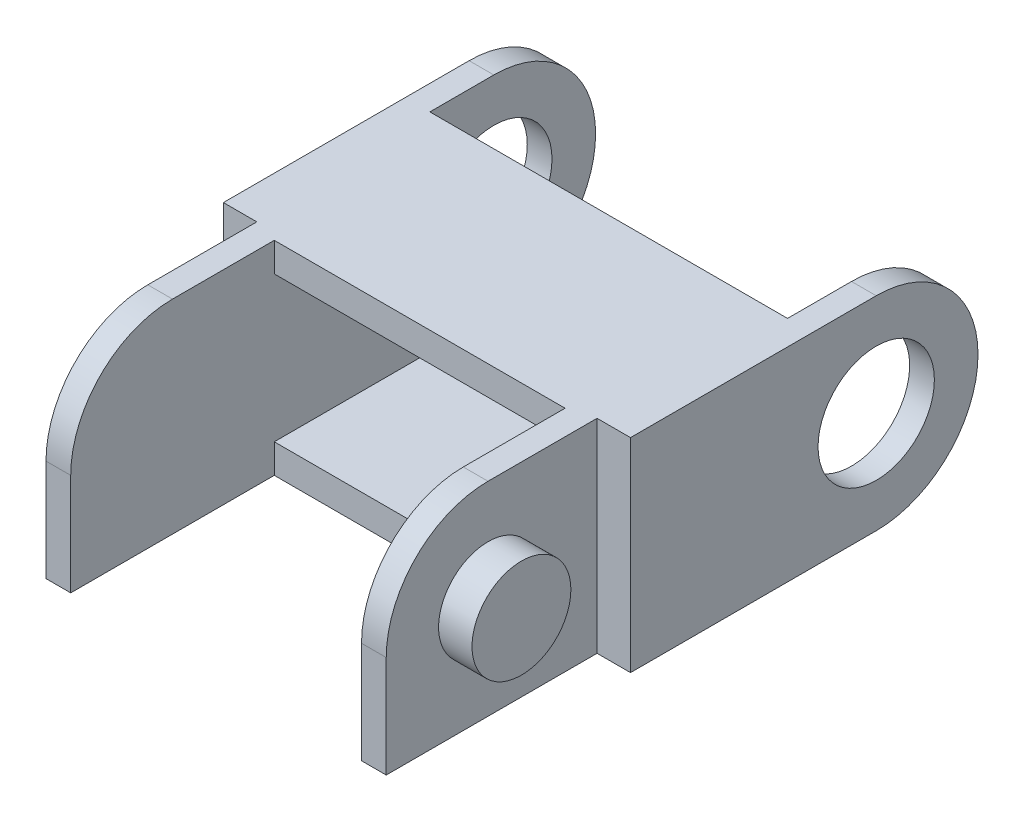
SolidWorks part; units mm, degrees
ref_plane "Front Plane" through (0, 0, 0) normal (0, 0, 1) x (1, 0, 0)
ref_plane "Top Plane" through (0, 0, 0) normal (0, 1, 0) x (1, 0, 0)
ref_plane "Right Plane" through (0, 0, 0) normal (1, 0, 0) x (0, 0, -1)
sketch "Sketch1" plane through (0, 0, 0) normal (0, 0, 1) x (1, 0, 0)
  line L0 (-12, 7) -> (12, 7)
  line L1 (-10, -5) -> (10, -5)
  line L2 (-10, -5) -> (-10, 5)
  line L3 (-10, 5) -> (10, 5)
  line L4 (10, -5) -> (10, 5)
  line L5 (-10, -5) -> (10, 5) construction
  line L6 (-10, 5) -> (10, -5) construction
  line L7 (12, -7) -> (12, 7)
  line L8 (-12, -7) -> (12, -7)
  line L9 (-12, -7) -> (-12, 7)
  point P0 (0, 0)
  dimension "D2" = 10
  dimension "D3" = 20
  dimension "D1" = 2
extrude "Boss-Extrude1" add sketch "Sketch1" along normal mid plane 10
sketch "Sketch3" plane through (12, 0, 0) normal (1, 0, 0) x (0, 0, -1)
  line L0 (-5, -7) -> (-5, 7)
  line L3 (-12, 7) -> (-5, 7)
  line L6 (-5, -7) -> (-19, -7)
  line L7 (-19, -7) -> (-19, 0)
  arc A1 (-19, 0) -> (-12, 7) centre (-12, 0) cw
extrude "Boss-Extrude3" add sketch "Sketch3" against normal blind 2
sketch "Sketch2" plane through (12, 0, 0) normal (1, 0, 0) x (0, 0, -1)
  line L4 (12.4, 7) -> (-5, 7)
  line L5 (-5, 7) -> (-5, -7)
  line L6 (-5, -7) -> (12.4, -7)
  line L9 (5.4, -7) -> (5.4, 7)
  line L10 (5.4, -7) -> (5.4, 7) construction
  arc A0 (12.4, -7) -> (12.4, 7) centre (12.4, 0) ccw
  circle A1 centre (12.4, 0) radius 4
  point P7 (0, 0)
  dimension "D1" = 3
  dimension "D2" = 0.4
extrude "Boss-Extrude2" add sketch "Sketch2" along normal blind 2
sketch "Sketch4" plane through (12, 0, 0) normal (1, 0, 0) x (0, 0, -1)
  circle A0 centre (-12, 0) radius 4 construction
  circle A1 centre (12.4, 0) radius 4 construction
  circle A2 centre (-12, 0) radius 3.4
  dimension "D1" = 0.6
extrude "Boss-Extrude4" add sketch "Sketch4" along normal through all
sketch "Sketch5" plane through (12, 0, 0) normal (1, 0, 0) x (0, 0, -1)
  line L4 (-5, -7) -> (-5, 7)
  line L5 (-5, 7) -> (-12, 7)
  line L6 (-19, 0) -> (-19, -7)
  line L7 (-19, -7) -> (-5, -7)
  line L8 (-5, -7) -> (-5, 7)
  line L9 (-5, 7) -> (-12, 7)
  line L11 (-19, -7) -> (-5, -7)
  line L12 (-19, 0) -> (-19, -7)
  arc A1 (-12, 7) -> (-19, 0) centre (-12, 0) ccw
  arc A2 (-12, 7) -> (-19, 0) centre (-12, 0) ccw
  circle A3 centre (-12, 0) radius 3.4
  circle A4 centre (-12, 0) radius 3.4
  dimension "D1" = 0
  dimension "D2" = 0
extrude "Cut-Extrude1" cut sketch "Sketch5" against normal blind 0.3
sketch "Sketch6" plane through (12, 0, 0) normal (-1, 0, 0) x (0, 0, 1)
  line L3 (-12.4, -7) -> (-5, -7)
  line L4 (-5, -7) -> (-5, 7)
  line L5 (-5, 7) -> (-12.4, 7)
  line L6 (-12.4, -7) -> (-5, -7)
  line L7 (-5, -7) -> (-5, 7)
  line L8 (-5, 7) -> (-12.4, 7)
  circle A0 centre (-12.4, 0) radius 4 construction
  arc A1 (-12.4, 7) -> (-12.4, -7) centre (-12.4, 0) ccw
  arc A2 (-12.4, 7) -> (-12.4, -7) centre (-12.4, 0) ccw
  circle A3 centre (-12.4, 0) radius 4
  dimension "D1" = 0
extrude "Cut-Extrude2" cut sketch "Sketch6" against normal blind 0.3
sketch "Sketch7" plane through (14, 0, 0) normal (1, 0, 0) x (0, 0, -1)
  line L0 (-5, -7) -> (12.4, -7) construction
  line L1 (-5, 7) -> (-4.5, 7)
  line L2 (-5, 7) -> (-5, -7)
  line L3 (-5, -7) -> (-4.5, -7)
  line L4 (-4.5, 7) -> (-4.5, -7)
  dimension "D1" = 0.5
extrude "Cut-Extrude3" cut sketch "Sketch7" against normal up to surface (2.3 mm away) up to face at (11.7, 0, 8.6)
mirror "Mirror1" about plane through (0, 0, 0) normal (1, 0, 0) of "Cut-Extrude3", "Boss-Extrude3", "Boss-Extrude2", "Boss-Extrude4", "Cut-Extrude1", "Cut-Extrude2"
sketch "Sketch8" plane through (0, 7, 0) normal (0, 1, 0) x (1, 0, 0)
  line L0 (12.3, 5) -> (12.3, 12.4) construction
  line L1 (-12.3, 5) -> (12.3, 5)
  line L2 (-12.3, 5) -> (-12.3, 8)
  line L3 (-12.3, 8) -> (12.3, 8)
  line L4 (12.3, 5) -> (12.3, 8)
  dimension "D1" = 3
extrude "Boss-Extrude5" add sketch "Sketch8" against normal up to surface (2 mm away) up to face at (0, 5, 0)
fillet "Fillet1" radius 5 1 edges at (0, 5, -8)
